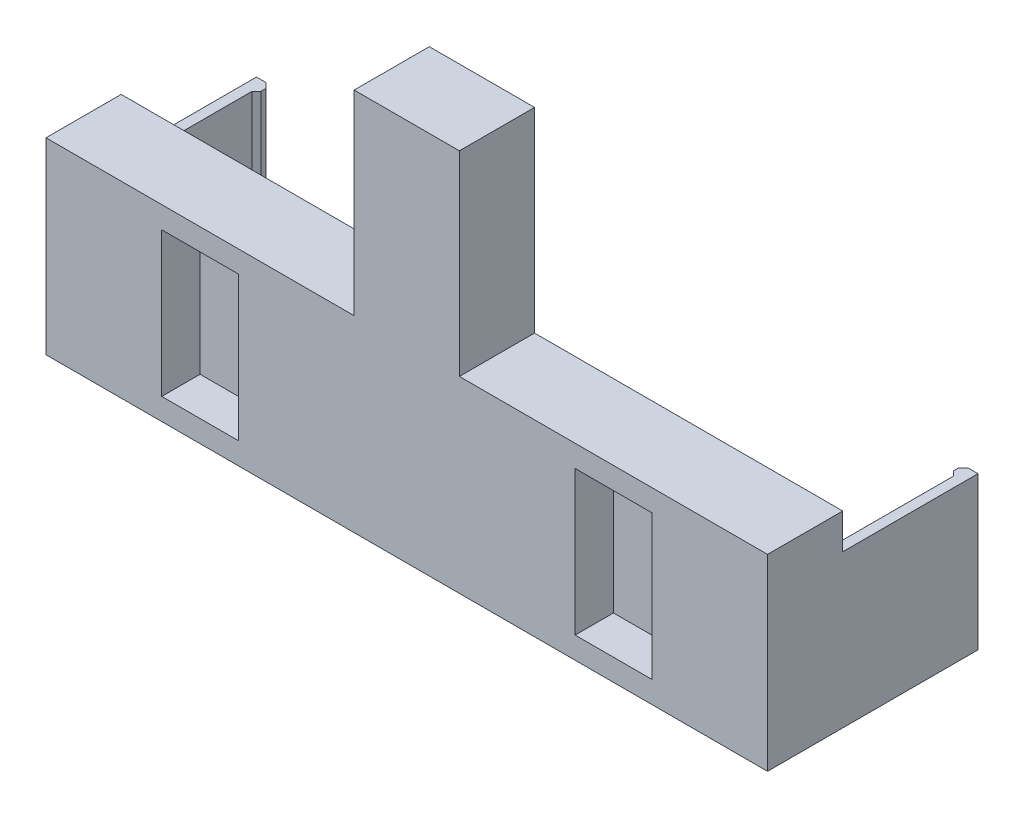
SolidWorks part; units mm, degrees
ref_plane "Front Plane" through (0, 0, 0) normal (0, 0, 1) x (1, 0, 0)
ref_plane "Top Plane" through (0, 0, 0) normal (0, 1, 0) x (1, 0, 0)
ref_plane "Right Plane" through (0, 0, 0) normal (1, 0, 0) x (0, 0, -1)
sketch "Display Rough Dim" plane through (0, 0, 0) normal (0, 0, 1) x (1, 0, 0)
  line L1 (-46.5, 48.5) -> (46.5, 48.5)
  line L2 (-46.5, 48.5) -> (-46.5, -48.5)
  line L3 (-46.5, -48.5) -> (46.5, -48.5)
  line L4 (46.5, 48.5) -> (46.5, -48.5)
  line L5 (-46.5, 48.5) -> (46.5, -48.5) construction
  line L6 (-46.5, -48.5) -> (46.5, 48.5) construction
  point P0 (0, 0)
  dimension "D1" = 93
  dimension "D2" = 97
sketch "Sketch1" plane through (0, 0, 0) normal (0, 0, 1) x (1, 0, 0)
  line L0 (-46.5, 48.5) -> (46.5, 48.5) construction
  line L1 (-48, 12.5) -> (48, 12.5)
  line L2 (-48, 12.5) -> (-48, -12.5)
  line L3 (-48, -12.5) -> (48, -12.5)
  line L4 (48, 12.5) -> (48, -12.5)
  line L5 (-48, 12.5) -> (48, -12.5) construction
  line L6 (-48, -12.5) -> (48, 12.5) construction
  line L7 (-7, 12.5) -> (-7, 38.5)
  line L8 (-7, 38.5) -> (7, 38.5)
  line L9 (7, 38.5) -> (7, 12.5)
  line L10 (46.5, 12.5) -> (46.5, -12.5)
  line L11 (46.5, 48.5) -> (46.5, -48.5) construction
  line L12 (-46.5, 12.5) -> (-46.5, -12.5)
  line L13 (-46.5, 48.5) -> (-46.5, -48.5) construction
  circle A0 centre (0, 31.5) radius 2
  point P0 (0, 0)
  point P14 (0, 38.5)
  dimension "D3" = 17
  dimension "D4" = 4
  dimension "D6" = 7
  dimension "D1" = 96
  dimension "D2" = 25
  dimension "D5" = 7
extrude "Boss-Extrude1" add sketch "Sketch1" along normal blind 10 contours L1 L12 L3 L10 | L12 L1 L2 L3 | L1 L10 L3 L4 | L9 L8 L7 L1 A0 | A0 region at (-47.25, 0, 0) region at (0, 0, 0) region at (0, 25.2855, 0) region at (47.25, 0, 0) region at (0, 31.5, 0)
extrude "Boss-Extrude2" add sketch "Sketch1<3>" against normal blind 18 contours L1 L10 L3 L4 | L12 L1 L2 L3 region at (-47.25, 0, 0) region at (47.25, 0, 0)
sketch "Sketch1<3>" plane through (0, 0, 0) normal (0, 0, 1) x (1, 0, 0) same geometry as "Sketch1"
extrude "Boss-Extrude3" add sketch "Sketch1<4>" against normal blind 5 contours A0
sketch "Sketch1<4>" plane through (0, 0, 0) normal (0, 0, 1) x (1, 0, 0) same geometry as "Sketch1"
sketch "Sketch5" plane through (0, 12.5, 0) normal (0, 1, 0) x (1, 0, 0)
  line L0 (-46.5, 18) -> (-45.5, 17)
  line L1 (-45.5, 17) -> (-46.5, 16)
  line L2 (-46.5, 18) -> (-46.5, 0) construction
  line L3 (-46.5, 16) -> (-43, 16) construction
  line L4 (-43, 16) -> (-43, 18) construction
  line L5 (-43, 18) -> (-46.5, 16) construction
  line L6 (-45.9, 17.4) -> (-45.9, 16.6)
  line L7 (0, 0) -> (0, 13.3207) construction
  line L8 (-48, 0) -> (48, 0) construction
  line L9 (45.5, 17) -> (46.5, 16)
  line L10 (46.5, 18) -> (45.5, 17)
  line L11 (45.9, 17.4) -> (45.9, 16.6)
  line L12 (46.5, 16) -> (46.5, 18)
  line M7 (-46.5, 0) -> (-46.5, 18)
  dimension "D1" = 3.5
  dimension "D2" = 2
  dimension "D3" = 135
  dimension "D4" = 0.6
extrude "Boss-Extrude4" add sketch "Sketch5" along direction (0, -1, 0) on the side against the normal up to surface (25 mm away) contours L9 L12 L10 L11 | L6 L0 L1 M7 region at (-46.2429, 12.5, -17) region at (46.2429, 12.5, -17) up to face at (0, -12.5, -6.5)
sketch "Sketch7" plane through (0, 12.5, 0) normal (0, 1, 0) x (1, 0, 0)
  line L0 (46.5, 0) -> (48, 0)
  line L1 (-48, 0) -> (48, 0) construction
  line L3 (-46.5, 0) -> (-48, 0)
  line L4 (-48, 0) -> (48, 0) construction
  line L12 (46.5, 0) -> (7, 0)
  line L13 (7, 0) -> (7, -10)
  line L14 (7, -10) -> (48, -10)
  line L15 (48, -10) -> (48, 18)
  line L16 (48, 18) -> (46.5, 18)
  line L17 (46.5, 18) -> (45.9, 17.4)
  line L18 (45.9, 17.4) -> (45.9, 16.6)
  line L19 (45.9, 16.6) -> (46.5, 16)
  line L20 (46.5, 16) -> (46.5, 0)
  line L21 (46.5, 0) -> (7, 0)
  line L22 (7, 0) -> (7, -10)
  line L23 (7, -10) -> (48, -10)
  line L24 (48, -10) -> (48, 18)
  line L25 (48, 18) -> (46.5, 18)
  line L26 (46.5, 18) -> (45.9, 17.4)
  line L27 (45.9, 17.4) -> (45.9, 16.6)
  line L28 (45.9, 16.6) -> (46.5, 16)
  line L29 (46.5, 16) -> (46.5, 0)
  line L30 (-7, 0) -> (-46.5, 0)
  line L31 (-46.5, 0) -> (-46.5, 16)
  line L32 (-46.5, 16) -> (-45.9, 16.6)
  line L33 (-45.9, 16.6) -> (-45.9, 17.4)
  line L34 (-45.9, 17.4) -> (-46.5, 18)
  line L35 (-46.5, 18) -> (-48, 18)
  line L36 (-48, 18) -> (-48, -10)
  line L37 (-48, -10) -> (-7, -10)
  line L38 (-7, -10) -> (-7, 0)
  line L39 (-7, 0) -> (-46.5, 0)
  line L40 (-46.5, 0) -> (-46.5, 16)
  line L41 (-46.5, 16) -> (-45.9, 16.6)
  line L42 (-45.9, 16.6) -> (-45.9, 17.4)
  line L43 (-45.9, 17.4) -> (-46.5, 18)
  line L44 (-46.5, 18) -> (-48, 18)
  line L45 (-48, 18) -> (-48, -10)
  line L46 (-48, -10) -> (-7, -10)
  line L47 (-7, -10) -> (-7, 0)
  line M22 (48, -10) -> (48, 18)
  line M23 (48, 18) -> (46.5, 18)
  line M24 (46.5, 18) -> (45.9, 17.4)
  line M25 (45.9, 17.4) -> (45.9, 16.6)
  line M26 (45.9, 16.6) -> (46.5, 16)
  line M27 (46.5, 16) -> (46.5, 0)
  dimension "D1" = 0
  dimension "D2" = 0
extrude "Cut-Extrude1" cut sketch "Sketch7" against normal blind 4.7 contours L0 M27 M22 M23 M24 M25 M26 region at (47.2196, 12.5, -9.2414)
extrude "Cut-Extrude2" cut sketch "Sketch7<4>" against normal blind 7 contours L44 L45 L3 L40 L41 L42 L43 region at (-47.2196, 12.5, -9.2414)
sketch "Sketch7<4>" plane through (0, 12.5, 0) normal (0, 1, 0) x (1, 0, 0) same geometry as "Sketch7"
sketch "Sketch8" plane through (0, 0, 10) normal (0, 0, 1) x (1, 0, 0)
  line L0 (-27.5, 12.5) -> (-27.5, 0) construction
  line L1 (-32.5, 9.5) -> (-22.5, 9.5)
  line L2 (-32.5, 9.5) -> (-32.5, -9.5)
  line L3 (-32.5, -9.5) -> (-22.5, -9.5)
  line L4 (-22.5, 9.5) -> (-22.5, -9.5)
  line L5 (-32.5, 9.5) -> (-22.5, -9.5) construction
  line L6 (-32.5, -9.5) -> (-22.5, 9.5) construction
  line L7 (-48, 12.5) -> (-7, 12.5) construction
  line L8 (27.5, 12.5) -> (27.5, 0) construction
  line L9 (7, 12.5) -> (48, 12.5) construction
  line L11 (22.5, 9.5) -> (32.5, 9.5)
  line L12 (22.5, 9.5) -> (22.5, -9.5)
  line L13 (22.5, -9.5) -> (32.5, -9.5)
  line L14 (32.5, 9.5) -> (32.5, -9.5)
  line L15 (22.5, 9.5) -> (32.5, -9.5) construction
  line L16 (22.5, -9.5) -> (32.5, 9.5) construction
  point P0 (-27.5, 0)
  point P18 (0, 0)
  point P19 (0, 0)
  dimension "D1" = 10
  dimension "D2" = 19
extrude "Cut-Extrude3" cut sketch "Sketch8" against normal blind 5
other "Move Face1" flip direction yes face at (2, 31.5, -5) face at (2, 31.5, -5) face at (-46.2, -3.5, -17.7) face at (-45.9, -3.5, -17) face at (-46.2, -3.5, -16.3) face at (-46.5, -3.5, -8) face at (46.2, -2.35, -17.7) face at (45.9, -2.35, -17) face at (46.2, -2.35, -16.3) face at (46.5, -2.35, -8) offset 0.15 parameters "D1"=0.15
other "Move Face2" flip direction yes face at (-22.5, 0, 7.5) face at (-32.5, 0, 7.5) face at (27.5, -9.5, 7.5) face at (22.5, 0, 7.5) face at (32.5, 0, 7.5) face at (27.5, 9.5, 7.5) face at (27.5, 0, 5) face at (-27.5, -9.5, 7.5) face at (-27.5, 9.5, 7.5) face at (-27.5, 0, 5) offset 0.1 parameters "D1"=0.1
equation "\"DisplayHeight\"= 18mm"
equation "\"DisplayWidth\"= 93mm"
equation "\"DisplayTall\"= 97mm"
